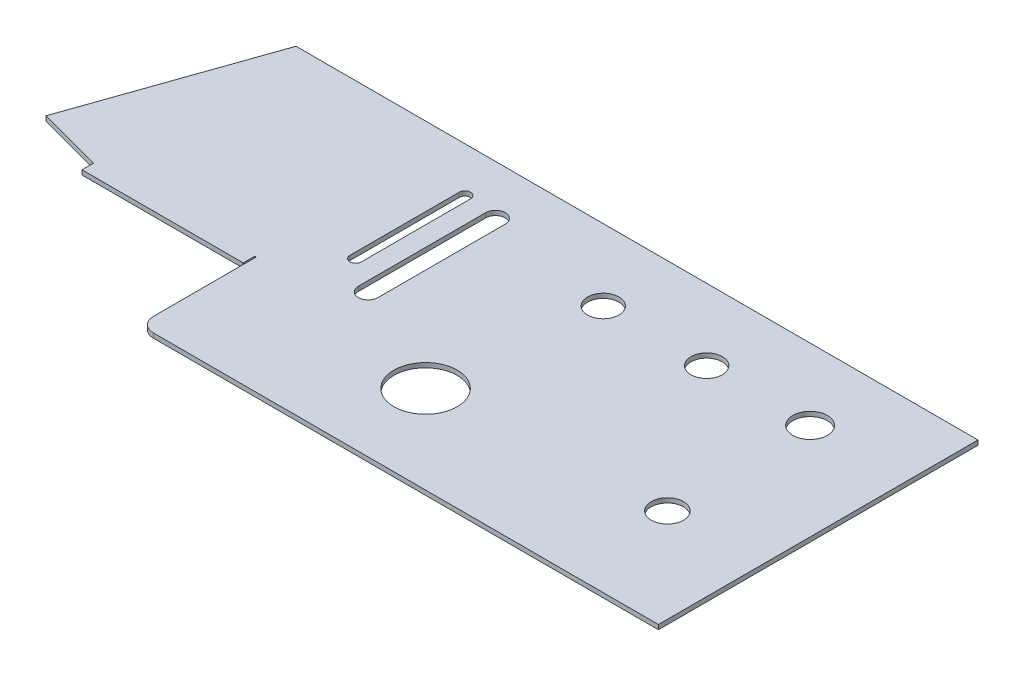
SolidWorks part; units mm, degrees
ref_plane "Front Plane" through (0, 0, 0) normal (0, 0, 1) x (1, 0, 0)
ref_plane "Top Plane" through (0, 0, 0) normal (0, 1, 0) x (1, 0, 0)
ref_plane "Right Plane" through (0, 0, 0) normal (1, 0, 0) x (0, 0, -1)
sketch "Sketch1" plane through (0, 0, 0) normal (0, 1, 0) x (1, 0, 0)
  line L0 (-101.3722, -12.5155) -> (-44.3722, -12.5155) construction
  line L1 (-44.3722, -53.5155) -> (137.6278, -53.5155) construction
  line L2 (-101.3722, -12.5155) -> (-101.3722, 58.4845) construction
  line L3 (-101.3722, 58.4845) -> (137.6278, 58.4845) construction
  line L4 (137.6278, -53.5155) -> (137.6278, 58.4845) construction
  line L5 (-44.3722, -12.5155) -> (-44.3722, -53.5155) construction
  line L6 (-26.4722, 42.7845) -> (-26.4722, 4.4845) construction
  line L7 (-23.4722, 42.7845) -> (-23.4722, 4.4845) construction
  line L8 (-29.4722, 42.7845) -> (-29.4722, 4.4845) construction
  line L9 (-14.1722, 41.1845) -> (-14.1722, -3.4155) construction
  line L10 (-9.5722, 41.1845) -> (-9.5722, -3.4155) construction
  line L11 (-18.7722, 41.1845) -> (-18.7722, -3.4155) construction
  line L12 (-26.4722, 45.7845) -> (-43.4588, 45.7845) construction
  line L13 (-26.4722, 1.4845) -> (-43.4588, 1.4845) construction
  line L14 (-14.1722, -8.0155) -> (-3.3024, -8.0155) construction
  line L15 (-14.1722, 45.7845) -> (0, 45.7845) construction
  line L16 (31.286, 33.4845) -> (122.5273, 33.4845) construction
  arc A0 (-23.4722, 42.7845) -> (-29.4722, 42.7845) centre (-26.4722, 42.7845) ccw construction
  arc A1 (-29.4722, 4.4845) -> (-23.4722, 4.4845) centre (-26.4722, 4.4845) ccw construction
  arc A2 (-9.5722, 41.1845) -> (-18.7722, 41.1845) centre (-14.1722, 41.1845) ccw construction
  arc A3 (-18.7722, -3.4155) -> (-9.5722, -3.4155) centre (-14.1722, -3.4155) ccw construction
  circle A7 centre (25.1778, -22.6655) radius 11.15 construction
  circle A8 centre (104.7278, -17.4655) radius 5.95 construction
  circle A9 centre (31.286, 33.4845) radius 6.25 construction
  circle A10 centre (67.536, 33.4845) radius 6.25 construction
  circle A11 centre (103.786, 33.4845) radius 6.25 construction
  point P0 (0, 0)
  point P10 (-26.4722, 23.6345)
  point P15 (-14.1722, 18.8845)
  dimension "D5" = 3
  dimension "D6" = 4.6
  dimension "D7" = 44.3
  dimension "D9" = 12.5
  dimension "D10" = 22.3
  dimension "D11" = 11.9
  dimension "D14" = 149.1
  dimension "D16" = 12.7
  dimension "D19" = 81.15
  dimension "D1" = 239
  dimension "D2" = 182
  dimension "D3" = 74.9
  dimension "D4" = 87.2
  dimension "D8" = 53.8
  dimension "D12" = 112
  dimension "D13" = 69.55
  dimension "D15" = 12.7
  dimension "D17" = 25
  dimension "D20" = 75.95
  dimension "D21" = 71
  dimension "D22" = 41
  dimension "D18" = 3
sketch "Sketch2" plane through (0, 0, 0) normal (0, 1, 0) x (1, 0, 0)
  line L0 (-44.8722, -12.5155) -> (-44.3722, -12.5155)
  line L1 (-101.3722, 58.4845) -> (137.6278, 58.4845)
  line L3 (-39.3722, -53.5155) -> (137.6278, -53.5155)
  line L4 (137.6278, 58.4845) -> (137.6278, -53.5155)
  line L5 (-44.3722, -12.5155) -> (-44.3722, -48.5155)
  line L6 (-26.4722, 4.4845) -> (-26.4722, 42.7845) construction
  line L7 (-28.4722, 4.4845) -> (-28.4722, 42.7845)
  line L8 (-24.4722, 4.4845) -> (-24.4722, 42.7845)
  line L9 (-14.1722, 41.1845) -> (-14.1722, -3.4155) construction
  line L10 (-10.7222, 41.1845) -> (-10.7222, -3.4155)
  line L11 (-17.6222, 41.1845) -> (-17.6222, -3.4155)
  line L12 (-101.3722, -12.5155) -> (-101.3722, -16.5155)
  line L13 (-101.3722, -16.5155) -> (-44.8722, -16.5155)
  line L14 (-44.8722, -16.5155) -> (-44.8722, -12.5155)
  line L15 (-101.3722, -12.5155) -> (-124.0715, -6.4333)
  line L16 (-124.0715, -6.4333) -> (-101.3722, 58.4845)
  arc A0 (-28.4722, 4.4845) -> (-24.4722, 4.4845) centre (-26.4722, 4.4845) ccw
  arc A1 (-24.4722, 42.7845) -> (-28.4722, 42.7845) centre (-26.4722, 42.7845) ccw
  arc A2 (-10.7222, 41.1845) -> (-17.6222, 41.1845) centre (-14.1722, 41.1845) ccw
  arc A3 (-17.6222, -3.4155) -> (-10.7222, -3.4155) centre (-14.1722, -3.4155) ccw
  circle A4 centre (31.286, 33.4845) radius 5.5
  circle A5 centre (67.536, 33.4845) radius 5.5
  circle A6 centre (103.786, 33.4845) radius 6.05
  circle A7 centre (25.1778, -22.6655) radius 11.1
  circle A8 centre (104.7278, -17.4655) radius 5.65
  arc A11 (-44.3722, -48.5155) -> (-39.3722, -53.5155) centre (-39.3722, -48.5155) ccw
  point P15 (-26.4722, 23.6345)
  point P24 (-14.1722, 18.8845)
  point P50 (-44.3722, -53.5155)
  dimension "D1" = 2
  dimension "D2" = 3.45
  dimension "D3" = 11
  dimension "D4" = 11
  dimension "D5" = 12.1
  dimension "D6" = 22.2
  dimension "D7" = 11.3
  dimension "D8" = 5
  dimension "D9" = 4
  dimension "D10" = 0.5
  dimension "D12" = 23.5
extrude "Boss-Extrude1" add sketch "Sketch2" along normal blind 1.6
